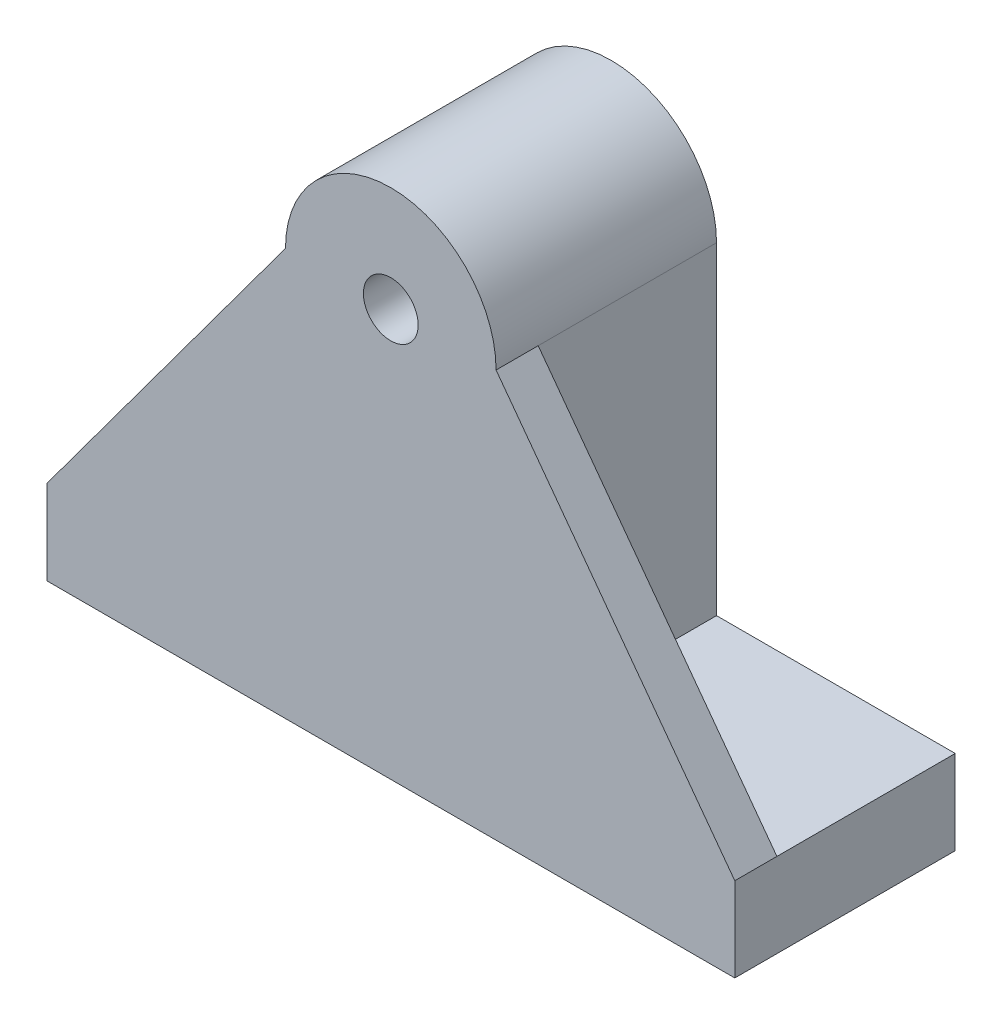
SolidWorks part; units mm, degrees
ref_plane "Front Plane" through (0, 0, 0) normal (0, 0, 1) x (1, 0, 0)
ref_plane "Top Plane" through (0, 0, 0) normal (0, 1, 0) x (1, 0, 0)
ref_plane "Right Plane" through (0, 0, 0) normal (1, 0, 0) x (0, 0, -1)
sketch "Sketch1" plane through (0, 0, 0) normal (0, 0, 1) x (1, 0, 0)
  line L0 (-7.5, 0) -> (-7.5, -29)
  line L1 (-7.5, -29) -> (24.5, -29)
  line L2 (24.5, -29) -> (24.5, -23)
  line L3 (24.5, -23) -> (7.5, -23)
  line L4 (7.5, -23) -> (7.5, 0)
  arc A0 (7.5, 0) -> (-7.5, 0) centre (0, 0) ccw
  dimension "D1" = 15
  dimension "D2" = 6
  dimension "D3" = 29
  dimension "D4" = 17
extrude "Main Body" add sketch "Sketch1" along normal blind 10.5 and the other way blind 10.5
sketch "Sketch2" plane through (0, 0, 10.5) normal (0, 0, 1) x (1, 0, 0)
  line L0 (7.5, 0) -> (24.5, -23)
rib "Rib1" sketch "Sketch2" sketch "Sketch2" thickness 3 extrusion direction parallel to sketch draft on no parameters "D1"=3
sketch "Sketch3" plane through (0, 0, -10.5) normal (0, 0, 1) x (1, 0, 0)
  arc A1 (7.5, 0) -> (-7.5, 0) centre (0, 0) ccw construction
  arc A2 (7.5, 0) -> (-7.5, 0) centre (0, 0) ccw construction
  circle A3 centre (0, 0) radius 7.5
extrude "Shaft" add sketch "Sketch3" against normal blind 8
mirror "Mirror2" about plane through (0, 0, 0) normal (1, 0, 0) of "Rib1", "Main Body"
sketch "Sketch5" plane through (0, 0, -10.5) normal (0, 0, -1) x (-1, 0, 0)
  line L7 (-7.5, 0) -> (-7.5, -23)
  line L8 (-7.5, -23) -> (-24.5, -23)
  line L9 (-24.5, -23) -> (-24.5, -29)
  line L10 (-24.5, -29) -> (24.5, -29)
  line L11 (24.5, -29) -> (24.5, -23)
  line L12 (24.5, -23) -> (7.5, -23)
  line L13 (7.5, -23) -> (7.5, 0)
  line L14 (-7.5, 0) -> (-7.5, -23)
  line L15 (-7.5, -23) -> (-24.5, -23)
  line L16 (-24.5, -23) -> (-24.5, -29)
  line L17 (-24.5, -29) -> (24.5, -29)
  line L18 (24.5, -29) -> (24.5, -23)
  line L19 (24.5, -23) -> (7.5, -23)
  line L20 (7.5, -23) -> (7.5, 0)
  arc A1 (-7.5, 0) -> (7.5, 0) centre (0, 0) ccw
  arc A2 (-7.5, 0) -> (7.5, 0) centre (0, 0) ccw
  dimension "D1" = 0
extrude "Cut-Extrude1" cut sketch "Sketch5" against normal offset from surface (5.3 mm away) 12.7 up to face at (13.1667, -15.3333, 7.5)
sketch "Sketch6" plane through (0, 0, -18.5) normal (0, 0, -1) x (-1, 0, 0)
  circle A0 centre (0, 0) radius 7.5 construction
  circle A1 centre (0, 0) radius 7.5
extrude "Cut-Extrude2" cut sketch "Sketch6" against normal up to surface (13.3 mm away) up to face at (0, -19.6875, -5.2)
sketch "Sketch7" plane through (0, 0, 10.5) normal (0, 0, 1) x (1, 0, 0)
  circle A1 centre (0, 0) radius 1.95
  arc A2 (7.5, 0) -> (-7.5, 0) centre (0, 0) ccw construction
  dimension "D1" = 3.9
extrude "Cut-Extrude3" cut sketch "Sketch7" against normal through all
